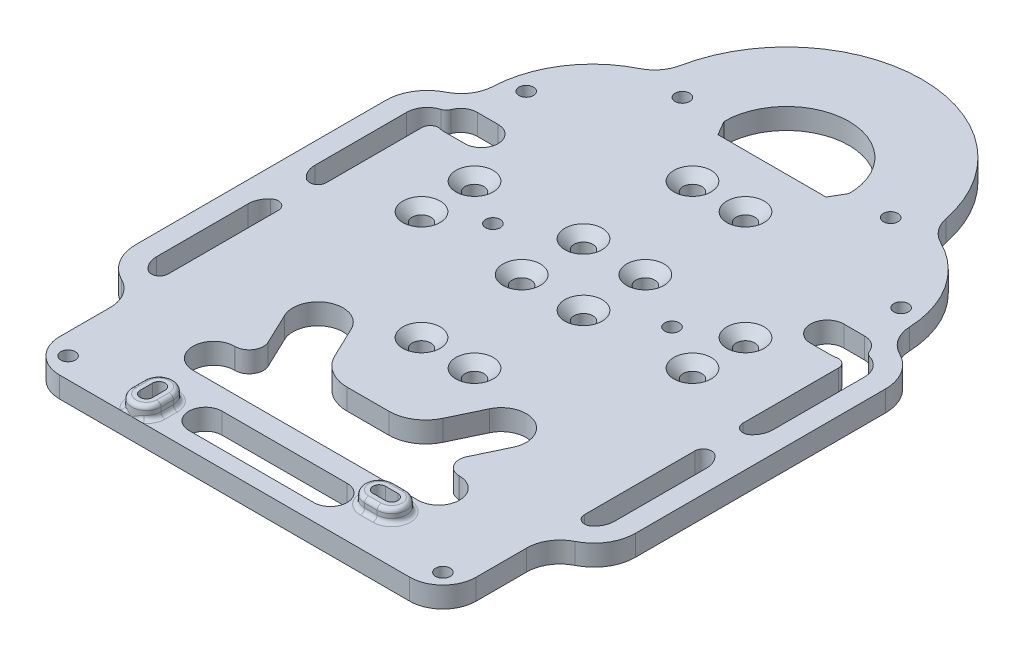
SolidWorks part; units mm, degrees
material "ABS"
ref_plane "Plano frontal" through (0, 0, 0) normal (0, 0, 1) x (1, 0, 0)
ref_plane "Plano superior" through (0, 0, 0) normal (0, 1, 0) x (1, 0, 0)
ref_plane "Plano direito" through (0, 0, 0) normal (1, 0, 0) x (0, 0, -1)
sketch "Esboço1" plane through (0, 0, 0) normal (0, 1, 0) x (1, 0, 0)
  line L1 (50, -48.75) -> (-50, -48.75)
  line L2 (50, -48.75) -> (50, 48.75)
  line L3 (50, 48.75) -> (-50, 48.75)
  line L4 (-50, -48.75) -> (-50, 48.75)
  line L5 (50, -48.75) -> (-50, 48.75) construction
  line L6 (50, 48.75) -> (-50, -48.75) construction
  point P0 (0, 0)
  dimension "D1" = 97.5
  dimension "D2" = 100
extrude "Ressalto-extrusão1" add sketch "Esboço1" along normal blind 5
hole_wizard "Escareado para SFHCS M41" positions "Esboço6" profile "Esboço5" countersink size "M4" standard "Ansi Metric"
sketch "Esboço6" plane through (0, 5, 0) normal (0, 1, 0) x (1, 0, 0)
  point P0 (-32.5269, 6.364)
  point P2 (-7.4246, 7.4246)
  point P4 (-6.364, 32.5269)
  point P6 (6.364, 32.5269)
  point P8 (7.4246, 7.4246)
  point P10 (32.5269, 6.364)
  point P12 (32.5269, -6.364)
  point P14 (7.4246, -7.4246)
  point P16 (6.364, -32.5269)
  point P18 (-6.364, -32.5269)
  point P20 (-32.5269, -6.364)
  point P22 (-7.4246, -7.4246)
sketch "Esboço5" plane through (-32.5269, 5, -6.364) normal (1, 0, 0) x (0, 0, 1)
  line L0 (0, 0) -> (0, 11.3519)
  line L1 (0, 11.3519) -> (2.25, 10)
  line L2 (2.25, 10) -> (2.25, 2.23)
  line L3 (2.25, 2.23) -> (4.48, 0)
  line L5 (4.48, 0) -> (0, 0)
  line L6 (-2.25, 2.23) -> (-4.48, 0) construction
  line L10 (0, 11.3519) -> (-2.25, 10) construction
  line L11 (0, -6.35) -> (0, 107.95) construction
  dimension "Hole Dia." = 4.5
  dimension "Hole Depth" = 10
  dimension "Near C'Sink Dia." = 8.96
  dimension "Near C'Sink Angle" = 90
  dimension "Drill Angle" = 118
sketch "Esboço3" plane through (0, 5, 0) normal (0, 1, 0) x (1, 0, 0)
  line L0 (-50, -48.75) -> (50, -48.75)
  line L1 (-50, -48.75) -> (-50, -83.75)
  line L2 (50, -48.75) -> (50, -83.75)
  line L3 (-50, -83.75) -> (50, -83.75)
  dimension "D1" = 35
extrude "Ressalto-extrusão3" add sketch "Esboço3" against normal up to surface (5 mm away) contours L1 L3 L2 L0 up to face at (-32.5269, 0, -4.114)
sketch "Esboço2" plane through (0, 5, 0) normal (0, 1, 0) x (1, 0, 0)
  line L0 (-55, -47.5) -> (-55, 12.5) construction
  line L1 (50, 48.75) -> (-50, 48.75) construction
  line L2 (-50, -47.5) -> (-50, 12.5) construction
  line L3 (-50, 48.75) -> (-50, -83.75) construction
  line L4 (-60, -47.5) -> (-60, 12.5)
  line L5 (-40, -47.5) -> (-40, 12.5)
  line L6 (0, 48.75) -> (0, -83.75) construction
  line L7 (-50, 12.5) -> (-50, -9.5) construction
  line L8 (-45, -47.5) -> (-45, 12.5) construction
  line L9 (50, -47.5) -> (50, 12.5) construction
  line L10 (60, -47.5) -> (60, 12.5)
  line L11 (40, -47.5) -> (40, 12.5)
  line L12 (45, -47.5) -> (45, 12.5) construction
  line L13 (55, -47.5) -> (55, 12.5) construction
  line L14 (-50, -83.75) -> (50, -83.75) construction
  line L15 (-45, 12.5) -> (-45, -9.5)
  line L16 (-55, 12.5) -> (-55, -9.5)
  line L17 (-50, 48.75) -> (-50, -83.75) construction
  line L18 (50, 12.5) -> (50, -9.5) construction
  line L19 (55, 12.5) -> (55, -9.5)
  line L20 (45, 12.5) -> (45, -9.5)
  line L21 (50, -25.5) -> (50, -47.5) construction
  line L22 (55, -25.5) -> (55, -47.5)
  line L23 (45, -25.5) -> (45, -47.5)
  line L24 (-50, -25.5) -> (-50, -47.5) construction
  line L25 (-45, -25.5) -> (-45, -47.5)
  line L26 (-55, -25.5) -> (-55, -47.5)
  line L27 (-32.5, 48.75) -> (32.5, 48.75)
  arc A0 (32.5, 48.75) -> (-32.5, 48.75) centre (0, 48.75) ccw
  arc A1 (-60, -47.5) -> (-40, -47.5) centre (-50, -47.5) ccw
  arc A2 (-40, 12.5) -> (-60, 12.5) centre (-50, 12.5) ccw
  arc A3 (-45, 12.5) -> (-55, 12.5) centre (-50, 12.5) ccw construction
  arc A4 (-55, -47.5) -> (-45, -47.5) centre (-50, -47.5) ccw construction
  arc A5 (60, -47.5) -> (40, -47.5) centre (50, -47.5) cw
  arc A6 (40, 12.5) -> (60, 12.5) centre (50, 12.5) cw
  arc A7 (55, -47.5) -> (45, -47.5) centre (50, -47.5) cw construction
  arc A8 (45, 12.5) -> (55, 12.5) centre (50, 12.5) cw construction
  arc A9 (-45, 12.5) -> (-55, 12.5) centre (-50, 12.5) ccw
  arc A10 (-55, -9.5) -> (-45, -9.5) centre (-50, -9.5) ccw
  arc A11 (55, 12.5) -> (45, 12.5) centre (50, 12.5) ccw
  arc A12 (45, -9.5) -> (55, -9.5) centre (50, -9.5) ccw
  arc A13 (55, -25.5) -> (45, -25.5) centre (50, -25.5) ccw
  arc A14 (45, -47.5) -> (55, -47.5) centre (50, -47.5) ccw
  arc A15 (-45, -25.5) -> (-55, -25.5) centre (-50, -25.5) ccw
  arc A16 (-55, -47.5) -> (-45, -47.5) centre (-50, -47.5) ccw
  point P8 (-50, -17.5)
  point P24 (50, -17.5)
  point P34 (-50, 1.5)
  point P47 (50, 1.5)
  point P54 (50, -36.5)
  point P61 (-50, -36.5)
  dimension "D1" = 65
  dimension "D2" = 10
  dimension "D5" = 8
  dimension "D3" = 60
  dimension "D4" = 5
  dimension "D6" = 2
  dimension "D7" = 2
extrude "Ressalto-extrusão2" add sketch "Esboço2" against normal up to surface (5 mm away) up to face at (-32.5269, 0, -4.114)
sketch "Esboço9" plane through (0, 5, 0) normal (0, 1, 0) x (1, 0, 0)
  line L0 (-15, -75.75) -> (15, -75.75) construction
  line L1 (-15, -71.75) -> (15, -71.75)
  line L2 (-15, -79.75) -> (15, -79.75)
  line L3 (-50, -83.75) -> (50, -83.75) construction
  line L4 (-46.5, 17) -> (-41.5, 17) construction
  line L5 (-46.5, 21) -> (-41.5, 21)
  line L6 (-46.5, 13) -> (-41.5, 13)
  line L7 (0, 81.25) -> (0, -83.75) construction
  line L8 (46.5, 17) -> (41.5, 17) construction
  line L9 (46.5, 21) -> (41.5, 21)
  line L10 (46.5, 13) -> (41.5, 13)
  arc A0 (-15, -71.75) -> (-15, -79.75) centre (-15, -75.75) ccw
  arc A1 (15, -79.75) -> (15, -71.75) centre (15, -75.75) ccw
  arc A2 (-46.5, 21) -> (-46.5, 13) centre (-46.5, 17) ccw
  arc A3 (-41.5, 13) -> (-41.5, 21) centre (-41.5, 17) ccw
  arc A4 (32.5, 48.75) -> (-32.5, 48.75) centre (0, 48.75) ccw construction
  arc A5 (46.5, 21) -> (46.5, 13) centre (46.5, 17) cw
  arc A6 (41.5, 13) -> (41.5, 21) centre (41.5, 17) cw
  point P2 (0, -75.75)
  point P9 (0, -83.75)
  point P12 (-44, 17)
  point P25 (44, 17)
  dimension "D1" = 4
  dimension "D5" = 4
  dimension "D2" = 30
  dimension "D3" = 4
  dimension "D4" = 5
  dimension "D7" = 44
  dimension "D8" = 17
extrude "Corte-extrusão1" cut sketch "Esboço9" against normal blind 10
hole_wizard "Furo de diâmetro Ø3.5 (3.5)1" positions "Esboço8" profile "Esboço7" hole size "Ø3.5" standard "Ansi Metric"
sketch "Esboço8" plane through (0, 5, 0) normal (0, 1, 0) x (1, 0, 0)
  line L1 (-45, 31.25) -> (45, 31.25)
  line L2 (-45, 31.25) -> (-45, -78.75)
  line L3 (-45, -78.75) -> (45, -78.75)
  line L4 (45, 31.25) -> (45, -78.75)
  line L5 (-50, -83.75) -> (50, -83.75) construction
  line L6 (-50, 15.0635) -> (-50, -14.5) construction
  line L7 (-32.5, 48.75) -> (-50, 48.75) construction
  line L9 (-21.5, -0.25) -> (21.5, -0.25)
  line L10 (-21.5, -0.25) -> (-21.5, -50.25)
  line L11 (-21.5, -50.25) -> (21.5, -50.25)
  line L12 (21.5, -0.25) -> (21.5, -50.25)
  circle A0 centre (0, 48.75) radius 25
  point P0 (-25, 48.75)
  point P2 (25, 48.75)
  point P11 (-45, 31.25)
  point P13 (45, 31.25)
  point P15 (-45, -78.75)
  point P17 (45, -78.75)
  point P88 (0, -78.75)
  point P91 (-21.5, -0.25)
  point P99 (21.5, -50.25)
  point P132 (-21.5, -50.25)
  point P133 (21.5, -0.25)
  point P135 (0, -0.25)
  dimension "D1" = 50
  dimension "D2" = 110
  dimension "D3" = 5
  dimension "D4" = 90
  dimension "D5" = 28.5
  dimension "D6" = 49
  dimension "D7" = 50
sketch "Esboço7" plane through (-25, 5, -48.75) normal (1, 0, 0) x (0, 0, 1)
  line L0 (0, 0) -> (0, 26.0515)
  line L1 (0, 26.0515) -> (1.75, 25)
  line L2 (1.75, 25) -> (1.75, 0)
  line L5 (1.75, 0) -> (0, 0)
  line L10 (0, 26.0515) -> (-1.75, 25) construction
  line L11 (0, -6.35) -> (0, 107.95) construction
  dimension "Hole Dia." = 3.5
  dimension "Hole Depth" = 25
  dimension "Drill Angle" = 118
fillet "Filete2" radius 8 8 edges at (-50, 2.5, 57.5) (32.5, 2.5, -48.75) (-32.5, 2.5, -48.75) (-50, 2.5, -22.5) (50, 2.5, 57.5) (50, 2.5, -22.5) (50, 2.5, 83.75) (-50, 2.5, 83.75)
fillet "Filete3" radius 25 2 edges at (50, 2.5, -48.75) (-50, 2.5, -48.75)
fillet "Filete6" radius 2 10 edges at (-50, 2.5, 52.5) (-50, 2.5, 20.5) (50, 2.5, 52.5) (50, 2.5, 20.5) (-50.4714, 2.5, -17.4777) (-50, 2.5, 14.5) (50, 2.5, -15.0635) (50, 2.5, 14.5) (50.4714, 2.5, -17.4777) (-50, 2.5, -15.0635)
sketch "Esboço10" plane through (0, 5, 0) normal (0, 1, 0) x (1, 0, 0)
  line L0 (0, 81.25) -> (0, -83.75) construction
  line L1 (-42, -83.75) -> (42, -83.75) construction
  line L2 (5, -51.75) -> (-5, -51.75)
  line L3 (-12.9973, -46.7004) -> (-16.5828, -39.1705)
  line L4 (-27.4172, -44.3295) -> (-23.8318, -51.8593)
  line L5 (-26.9198, -56.75) -> (-27, -56.75)
  line L6 (-27, -66.75) -> (27, -66.75)
  line L7 (15, -71.75) -> (-15, -71.75) construction
  line L8 (26.9198, -56.75) -> (27, -56.75)
  line L9 (27.4172, -44.3295) -> (23.8318, -51.8593)
  line L10 (12.9973, -46.7004) -> (16.5828, -39.1705)
  line L11 (-15, 48.75) -> (-12.9793, 45.25)
  line L12 (-12.9793, 45.25) -> (12.9793, 45.25)
  line L13 (12.9793, 45.25) -> (15, 48.75)
  arc A0 (31.8596, 55.1698) -> (-31.8596, 55.1698) centre (0, 48.75) ccw construction
  arc A1 (-5, -51.75) -> (-12.9973, -46.7004) centre (-5, -42.8923) cw
  arc A2 (-16.5828, -39.1705) -> (-27.4172, -44.3295) centre (-22, -41.75) ccw
  arc A3 (-23.8318, -51.8593) -> (-26.9198, -56.75) centre (-26.9198, -53.3297) cw
  arc A4 (-27, -56.75) -> (-27, -66.75) centre (-27, -61.75) ccw
  arc A5 (27, -56.75) -> (27, -66.75) centre (27, -61.75) cw
  arc A6 (23.8318, -51.8593) -> (26.9198, -56.75) centre (26.9198, -53.3297) ccw
  arc A7 (16.5828, -39.1705) -> (27.4172, -44.3295) centre (22, -41.75) cw
  arc A8 (5, -51.75) -> (12.9973, -46.7004) centre (5, -42.8923) ccw
  arc A9 (15, 48.75) -> (-15, 48.75) centre (0, 48.75) ccw
  point P21 (0, -51.75)
  point P35 (0, -66.75)
  point P39 (0, 45.25)
  dimension "D3" = 6
  dimension "D4" = 5
  dimension "D6" = 3.4203
  dimension "D10" = 30
  dimension "D1" = 27
  dimension "D2" = 22
  dimension "D5" = 5
  dimension "D7" = 15
  dimension "D8" = 5
  dimension "D9" = 30
  dimension "D11" = 3.5
  dimension "D12" = 120
extrude "Corte-extrusão2" cut sketch "Esboço10" against normal blind 10
sketch "Esboço11" plane through (0, 5, 0) normal (0, 1, 0) x (1, 0, 0)
  line L0 (0, -83.75) -> (0, 0) construction
  line L1 (-42, -83.75) -> (42, -83.75) construction
  line L2 (23.2, -72.25) -> (26.2, -72.25) construction
  line L3 (23.2, -70.75) -> (26.2, -70.75)
  line L4 (23.2, -73.75) -> (26.2, -73.75)
  line L5 (23.2, -68.75) -> (26.2, -68.75)
  line L6 (23.2, -75.75) -> (26.2, -75.75)
  line L7 (-28.2, -80.25) -> (-28.2, -77.25)
  line L8 (-21.2, -80.25) -> (-21.2, -77.25)
  line L9 (42, -83.75) -> (-42, -83.75) construction
  line L10 (-24.7, -80.25) -> (-24.7, -77.25) construction
  line L11 (-26.2, -80.25) -> (-26.2, -77.25)
  line L12 (-23.2, -80.25) -> (-23.2, -77.25)
  arc A0 (-26.2, -80.25) -> (-23.2, -80.25) centre (-24.7, -80.25) ccw
  arc A1 (-23.2, -77.25) -> (-26.2, -77.25) centre (-24.7, -77.25) ccw
  arc A2 (23.2, -70.75) -> (23.2, -73.75) centre (23.2, -72.25) ccw
  arc A3 (26.2, -73.75) -> (26.2, -70.75) centre (26.2, -72.25) ccw
  arc A4 (26.2, -75.75) -> (26.2, -68.75) centre (26.2, -72.25) ccw
  arc A5 (23.2, -68.75) -> (23.2, -75.75) centre (23.2, -72.25) ccw
  arc A6 (-21.2, -77.25) -> (-28.2, -77.25) centre (-24.7, -77.25) ccw
  arc A7 (-28.2, -80.25) -> (-21.2, -80.25) centre (-24.7, -80.25) ccw
  point P7 (24.7, -72.25)
  point P15 (-24.7, -78.75)
  dimension "D5" = 1.5
  dimension "D6" = 1.5
  dimension "D1" = 24.7
  dimension "D2" = 3
  dimension "D3" = 5
  dimension "D4" = 3
  dimension "D7" = 24.7
  dimension "D9" = 11.5
  dimension "D8" = 2
extrude "Ressalto-extrusão4" add sketch "Esboço11" along normal blind 3
fillet "Filete7" radius 1 17 edges at (-28.2, 8, 78.75) (-21.2, 8, 78.75) (-28.2, 5, 78.75) (-21.2, 5, 78.75) (-24.7, 5, 73.75) (-24.7, 8, 73.75) (-24.7, 8, 83.75) (-27.1749, 5, 82.7249) (-22.2251, 5, 82.7249) (24.7, 8, 75.75) (24.7, 8, 68.75) (24.7, 5, 75.75) (24.7, 5, 68.75) (19.7, 5, 72.25) (19.7, 8, 72.25) (29.7, 8, 72.25) (29.7, 5, 72.25)
sketch "Esboço13" plane through (0, 8, 0) normal (0, 1, 0) x (-1, 0, 0)
  line L2 (23.2, 80.25) -> (23.2, 77.25) construction
  line L3 (26.2, 77.25) -> (26.2, 80.25) construction
  line L6 (-26.2, 70.75) -> (-23.2, 70.75) construction
  line L7 (-23.2, 73.75) -> (-26.2, 73.75) construction
  line L8 (23.2, 80.25) -> (23.2, 77.25)
  line L9 (26.2, 77.25) -> (26.2, 80.25)
  line L10 (-26.2, 70.75) -> (-23.2, 70.75)
  line L11 (-23.2, 73.75) -> (-26.2, 73.75)
  arc A2 (23.2, 77.25) -> (26.2, 77.25) centre (24.7, 77.25) ccw construction
  arc A3 (26.2, 80.25) -> (23.2, 80.25) centre (24.7, 80.25) ccw construction
  arc A6 (-23.2, 70.75) -> (-23.2, 73.75) centre (-23.2, 72.25) ccw construction
  arc A7 (-26.2, 73.75) -> (-26.2, 70.75) centre (-26.2, 72.25) ccw construction
  arc A8 (23.2, 77.25) -> (26.2, 77.25) centre (24.7, 77.25) ccw
  arc A9 (26.2, 80.25) -> (23.2, 80.25) centre (24.7, 80.25) ccw
  arc A10 (-23.2, 70.75) -> (-23.2, 73.75) centre (-23.2, 72.25) ccw
  arc A11 (-26.2, 73.75) -> (-26.2, 70.75) centre (-26.2, 72.25) ccw
extrude "Corte-extrusão3" cut sketch "Esboço13" against normal through all
equation "\"D4@Esboço11\"=\"D2@Esboço11\""
equation "\"D6@Esboço11\"=\"D5@Esboço11\""
